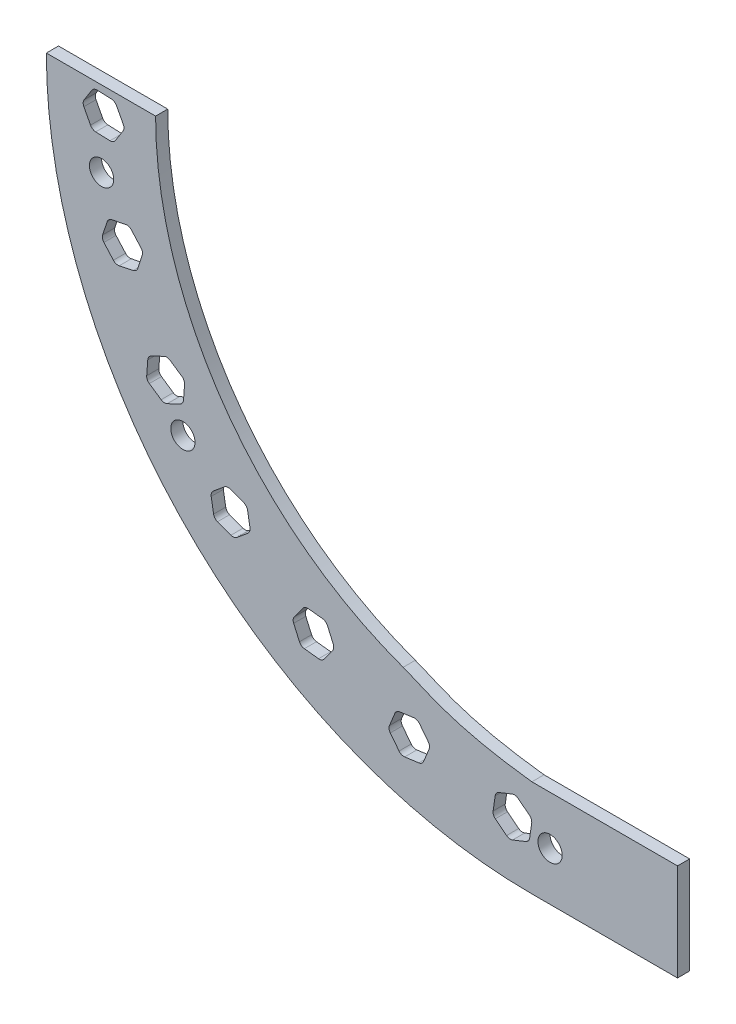
SolidWorks part; units mm, degrees
ref_plane "Front Plane" through (0, 0, 0) normal (0, 0, 1) x (1, 0, 0)
ref_plane "Top Plane" through (0, 0, 0) normal (0, 1, 0) x (1, 0, 0)
ref_plane "Right Plane" through (0, 0, 0) normal (1, 0, 0) x (0, 0, -1)
sketch "Layout" plane through (0, 0, 0) normal (0, 0, 1) x (1, 0, 0)
  line L0 (0, 0) -> (-76.2, 0) construction
  line L1 (-76.2, 0) -> (-203.2, 0) construction
  dimension "D1" = 76.2
  dimension "D2" = 127
sketch "Sketch1" plane through (0, 0, 0) normal (0, 0, 1) x (1, 0, 0)
  line L0 (0, 0) -> (-203.2, 0) construction
  line L1 (0, 0) -> (0, -203.2) construction
  line L2 (0, -203.2) -> (76.2, -203.2)
  line L3 (0, -254) -> (76.2, -254)
  line L4 (-254, 0) -> (-203.2, 0)
  line L5 (76.2, -203.2) -> (76.2, -254)
  arc A0 (-203.2, 0) -> (0, -203.2) centre (0, 0) ccw
  arc A1 (-254, 0) -> (0, -254) centre (0, 0) ccw
  dimension "D1" = 50.8
  dimension "D2" = 76.2
  dimension "D3" = 203.2
extrude "Boss-Extrude1" add sketch "Sketch1" along normal blind 6.35
sketch "Mid_Point_Sk" plane through (0, 0, 0) normal (0, 1, 0) x (1, 0, 0)
  line L0 (-254, 0) -> (-203.2, -6.35) construction
  line L1 (-254, -6.35) -> (-203.2, 0) construction
ref_point "Mid_Point"
ref_plane "Mid_Plane" through (0, 0, 3.175) normal (0, 0, 1) x (1, 0, 0)
sketch "Sketch2" plane through (0, 0, 6.35) normal (0, 0, 1) x (1, 0, 0)
  line L0 (0, 0) -> (-229.3095, 0) construction
  line L1 (0, 0) -> (-222.5647, -39.2442) construction
  line L2 (0, 0) -> (-173.1246, -145.2688) construction
  arc A0 (-222.5647, -39.2442) -> (-173.1246, -145.2688) centre (0, 0) ccw construction
  arc A1 (-222.5647, -39.2442) -> (-173.1246, -145.2688) centre (0, 0) ccw construction
  arc A2 (-228.8182, -40.3468) -> (-177.989, -149.3505) centre (0, 0) ccw
  arc A3 (-216.3112, -38.1415) -> (-168.2602, -141.1871) centre (0, 0) ccw
  arc A4 (-216.3112, -38.1415) -> (-228.8182, -40.3468) centre (-222.5647, -39.2442) ccw
  arc A5 (-177.989, -149.3505) -> (-168.2602, -141.1871) centre (-173.1246, -145.2688) ccw
  point P5 (-204.8238, -95.5109)
  dimension "D1" = 30
  dimension "D3" = 12.7
  dimension "D2" = 10
sketch "Sketch3" plane through (0, 0, 6.35) normal (0, 0, 1) x (1, 0, 0)
  line L0 (0, 0) -> (-225.1271, -39.696) construction
  line L1 (0, 0) -> (-182.5681, -137.5749) construction
  line L2 (-203.2, 0) -> (-254, 0) construction
  circle A1 centre (-182.5681, -137.5749) radius 6.35
  circle A3 centre (-225.1271, -39.696) radius 6.35
  dimension "D1" = 228.6
  dimension "D2" = 27
  dimension "D3" = 10
extrude "Cut-Extrude1" cut sketch "Sketch3" against normal up to next
sketch "Sketch4" plane through (0, 0, 6.35) normal (0, 0, 1) x (1, 0, 0)
  line L0 (0, -203.2) -> (0, -228.6) construction
  line L1 (0, -228.6) -> (9.525, -228.6) construction
  circle A1 centre (9.525, -228.6) radius 6.35
  dimension "D1" = 25.4
  dimension "D2" = 9.525
extrude "Cut-Extrude2" cut sketch "Sketch4" against normal up to next
sketch "Sketch5" plane through (0, 0, 6.35) normal (0, 0, 1) x (1, 0, 0)
  line L0 (0, 0) -> (-67.3267, -184.9785) construction
  line L2 (0, 0) -> (-196.85, 0) construction
  line L3 (-196.85, 0) -> (-203.2, 0)
  arc A0 (-67.3267, -184.9785) -> (-196.85, 0) centre (0, 0) cw
  arc A1 (-203.2, 0) -> (0, -203.2) centre (0, 0) ccw construction
  arc A2 (-203.2, 0) -> (0, -203.2) centre (0, 0) ccw
  spline S0 degree 3 poles (0, -203.2) (-42.7386, -198.0277) (-55.3777, -189.3302) (-67.3267, -184.9785) knots 0 0 0 0 1 1 1 1
  dimension "D1" = 70
  dimension "D2" = 196.85
extrude "Boss-Extrude2" add sketch "Sketch5" against normal up to surface (6.35 mm away) up to face at (15.875, -228.6, 0)
sketch "Sketch6" plane through (0, 0, 6.35) normal (0, 0, 1) x (1, 0, 0)
  line L0 (-204.5101, -63.4989) -> (-209.4922, -57.9153)
  line L1 (-217.9162, -21.638) -> (-213.9222, -15.3098)
  line L3 (-213.797, -12.1373) -> (-217.2803, -5.5142)
  line L4 (-219.9653, -3.8196) -> (-227.4427, -3.5247)
  line L5 (-230.2527, -5.0026) -> (-234.2468, -11.3308)
  line L6 (-234.3719, -14.5033) -> (-230.8886, -21.1264)
  line L7 (-228.2037, -22.821) -> (-220.7263, -23.1159)
  line L8 (-206.2085, -73.714) -> (-203.864, -66.6075)
  line L9 (-215.9042, -77.3506) -> (-208.5776, -75.8278)
  line L10 (-223.9014, -70.7722) -> (-218.9193, -76.3558)
  line L11 (-222.203, -60.5572) -> (-224.5475, -67.6636)
  line L12 (-212.5073, -56.9206) -> (-219.8339, -58.4434)
  line L13 (-183.0735, -111.0882) -> (-189.2584, -106.8757)
  line L14 (-182.2502, -121.4107) -> (-181.6945, -113.9481)
  line L15 (-190.7781, -127.2849) -> (-184.0375, -124.0348)
  line L16 (-200.1293, -122.8366) -> (-193.9443, -127.0491)
  line L17 (-200.9525, -112.5141) -> (-201.5082, -119.9767)
  line L18 (-192.4246, -106.6399) -> (-199.1652, -109.89)
  line L19 (-150.7607, -152.0779) -> (-157.781, -149.4868)
  line L20 (-147.4647, -161.8946) -> (-148.7309, -154.5193)
  line L21 (-154.3182, -169.6574) -> (-148.5641, -164.8732)
  line L22 (-164.4677, -167.6035) -> (-157.4474, -170.1946)
  line L23 (-167.7637, -157.7868) -> (-166.4975, -165.1621)
  line L24 (-160.9102, -150.024) -> (-166.6644, -154.8082)
  line L25 (-109.4915, -184.0329) -> (-116.9301, -183.2171)
  line L26 (-103.9185, -192.7606) -> (-106.9313, -185.9107)
  line L27 (-108.6904, -201.9508) -> (-104.2646, -195.9166)
  line L28 (-119.0353, -202.4133) -> (-111.5967, -203.2291)
  line L29 (-124.6083, -193.6856) -> (-121.5955, -200.5355)
  line L30 (-119.8364, -184.4954) -> (-124.2622, -190.5295)
  line L31 (-61.7176, -205.0547) -> (-69.1326, -206.0627)
  line L32 (-54.1987, -212.1749) -> (-58.7792, -206.2573)
  line L33 (-56.6055, -222.2466) -> (-53.771, -215.321)
  line L34 (-66.5313, -225.198) -> (-59.1163, -224.19)
  line L35 (-74.0502, -218.0778) -> (-69.4697, -223.9954)
  line L36 (-71.6433, -208.0061) -> (-74.4778, -214.9317)
  line L37 (-10.2771, -213.8945) -> (-17.228, -216.6664)
  line L38 (-1.259, -218.9843) -> (-7.135, -214.3506)
  line L39 (-1.1578, -229.339) -> (-0.0829, -221.9334)
  line L40 (-10.0747, -234.604) -> (-3.1238, -231.8321)
  line L41 (-19.0928, -229.5143) -> (-13.2168, -234.148)
  line L42 (-19.194, -219.1595) -> (-20.2688, -226.5651)
  line L43 (0, 0) -> (-213.797, -12.1373) construction
  line L44 (0, 0) -> (-204.5101, -63.4989) construction
  circle A0 centre (-224.0845, -13.3203) radius 9.6556 construction
  arc A1 (-209.4922, -57.9153) -> (-212.5073, -56.9206) centre (-211.8612, -60.0291) ccw
  arc A2 (-203.864, -66.6075) -> (-204.5101, -63.4989) centre (-206.8791, -65.6128) ccw
  arc A3 (-206.2085, -73.714) -> (-208.5776, -75.8278) centre (-209.2236, -72.7192) cw
  arc A4 (-218.9193, -76.3558) -> (-215.9042, -77.3506) centre (-216.5503, -74.242) ccw
  arc A5 (-224.5475, -67.6636) -> (-223.9014, -70.7722) centre (-221.5324, -68.6584) ccw
  arc A6 (-219.8339, -58.4434) -> (-222.203, -60.5572) centre (-219.1878, -61.5519) ccw
  arc A7 (-217.9162, -21.638) -> (-220.7263, -23.1159) centre (-220.6012, -19.9434) cw
  arc A8 (-230.8886, -21.1264) -> (-228.2037, -22.821) centre (-228.0786, -19.6485) ccw
  arc A9 (-234.2468, -11.3308) -> (-234.3719, -14.5033) centre (-231.5619, -13.0254) ccw
  arc A10 (-227.4427, -3.5247) -> (-230.2527, -5.0026) centre (-227.5678, -6.6972) ccw
  arc A11 (-217.2803, -5.5142) -> (-219.9653, -3.8196) centre (-220.0904, -6.9921) ccw
  arc A12 (-213.9222, -15.3098) -> (-213.797, -12.1373) centre (-216.6071, -13.6152) ccw
  arc A13 (-189.2584, -106.8757) -> (-192.4246, -106.6399) centre (-191.0457, -109.4999) ccw
  arc A14 (-181.6945, -113.9481) -> (-183.0735, -111.0882) centre (-184.8608, -113.7124) ccw
  arc A15 (-182.2502, -121.4107) -> (-184.0375, -124.0348) centre (-185.4164, -121.1749) cw
  arc A16 (-193.9443, -127.0491) -> (-190.7781, -127.2849) centre (-192.157, -124.425) ccw
  arc A17 (-201.5082, -119.9767) -> (-200.1293, -122.8366) centre (-198.342, -120.2125) ccw
  arc A18 (-199.1652, -109.89) -> (-200.9525, -112.5141) centre (-197.7863, -112.7499) ccw
  arc A19 (-157.781, -149.4868) -> (-160.9102, -150.024) centre (-158.8804, -152.4654) ccw
  arc A20 (-148.7309, -154.5193) -> (-150.7607, -152.0779) centre (-151.8601, -155.0565) ccw
  arc A21 (-147.4647, -161.8946) -> (-148.5641, -164.8732) centre (-150.5939, -162.4318) cw
  arc A22 (-157.4474, -170.1946) -> (-154.3182, -169.6574) centre (-156.348, -167.216) ccw
  arc A23 (-166.4975, -165.1621) -> (-164.4677, -167.6035) centre (-163.3683, -164.6249) ccw
  arc A24 (-166.6644, -154.8082) -> (-167.7637, -157.7868) centre (-164.6345, -157.2496) ccw
  arc A25 (-116.9301, -183.2171) -> (-119.8364, -184.4954) centre (-117.2762, -186.3732) ccw
  arc A26 (-106.9313, -185.9107) -> (-109.4915, -184.0329) centre (-109.8376, -187.1889) ccw
  arc A27 (-103.9185, -192.7606) -> (-104.2646, -195.9166) centre (-106.8248, -194.0389) cw
  arc A28 (-111.5967, -203.2291) -> (-108.6904, -201.9508) centre (-111.2506, -200.073) ccw
  arc A29 (-121.5955, -200.5355) -> (-119.0353, -202.4133) centre (-118.6892, -199.2572) ccw
  arc A30 (-124.2622, -190.5295) -> (-124.6083, -193.6856) centre (-121.702, -192.4073) ccw
  arc A31 (-69.1326, -206.0627) -> (-71.6433, -208.0061) centre (-68.7049, -209.2088) ccw
  arc A32 (-58.7792, -206.2573) -> (-61.7176, -205.0547) centre (-61.2899, -208.2008) ccw
  arc A33 (-54.1987, -212.1749) -> (-53.771, -215.321) centre (-56.7094, -214.1183) cw
  arc A34 (-59.1163, -224.19) -> (-56.6055, -222.2466) centre (-59.544, -221.0439) ccw
  arc A35 (-69.4697, -223.9954) -> (-66.5313, -225.198) centre (-66.959, -222.0519) ccw
  arc A36 (-74.4778, -214.9317) -> (-74.0502, -218.0778) centre (-71.5394, -216.1344) ccw
  arc A37 (-17.228, -216.6664) -> (-19.194, -219.1595) centre (-16.0519, -219.6156) ccw
  arc A38 (-7.135, -214.3506) -> (-10.2771, -213.8945) centre (-9.101, -216.8437) ccw
  arc A39 (-1.259, -218.9843) -> (-0.0829, -221.9334) centre (-3.225, -221.4774) cw
  arc A40 (-3.1238, -231.8321) -> (-1.1578, -229.339) centre (-4.2999, -228.883) ccw
  arc A41 (-13.2168, -234.148) -> (-10.0747, -234.604) centre (-11.2508, -231.6549) ccw
  arc A42 (-20.2688, -226.5651) -> (-19.0928, -229.5143) centre (-17.1268, -227.0212) ccw
  point P12 (0, 0)
  point P75 (-212.9438, -13.7597)
  dimension "D1" = 14
  dimension "D2" = 3.175
extrude "Cut-Extrude3" cut sketch "Sketch6" against normal through all
